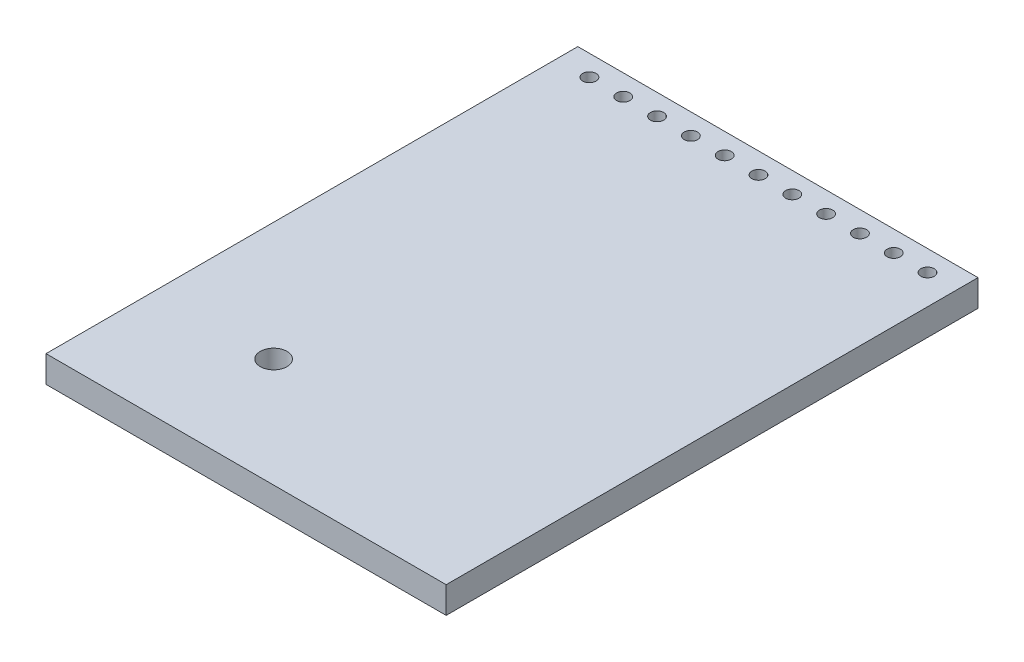
SolidWorks part; units mm, degrees
ref_plane "Front Plane" through (0, 0, 0) normal (0, 0, 1) x (1, 0, 0)
ref_plane "Top Plane" through (0, 0, 0) normal (0, 1, 0) x (1, 0, 0)
ref_plane "Right Plane" through (0, 0, 0) normal (1, 0, 0) x (0, 0, -1)
sketch "Sketch1" plane through (0, 0, 0) normal (0, 0, 1) x (1, 0, 0)
  line L1 (0, 0) -> (30.06, 0)
  line L2 (0, 0) -> (0, 2)
  line L3 (0, 2) -> (30.06, 2)
  line L4 (30.06, 0) -> (30.06, 2)
  dimension "D1" = 30.06
  dimension "D2" = 2
extrude "Boss-Extrude1" add sketch "Sketch1" along normal blind 39.95
sketch "Sketch2" plane through (0, 2, 0) normal (0, 1, 0) x (1, 0, 0)
  line L0 (0, -39.95) -> (0, 0) construction
  line L2 (30.06, -39.95) -> (0, -39.95) construction
  circle A0 centre (8.9, -31.75) radius 1
  dimension "D1" = 2
  dimension "D2" = 8.9
  dimension "D3" = 8.2
extrude "Cut-Extrude1" cut sketch "Sketch2" against normal blind 39.95
sketch "Sketch3" plane through (0, 2, 0) normal (0, 1, 0) x (1, 0, 0)
  line L0 (30.06, -39.95) -> (30.06, 0) construction
  line L1 (30.06, 0) -> (0, 0) construction
  circle A0 centre (27.83, -1.56) radius 0.5
  dimension "D1" = 1
  dimension "D2" = 2.23
  dimension "D3" = 1.56
extrude "Cut-Extrude2" cut sketch "Sketch3" against normal blind 4.5
pattern_linear "LPattern1" count 11 spacing 2.54 along (-1, 0, 0) of "Cut-Extrude2"
